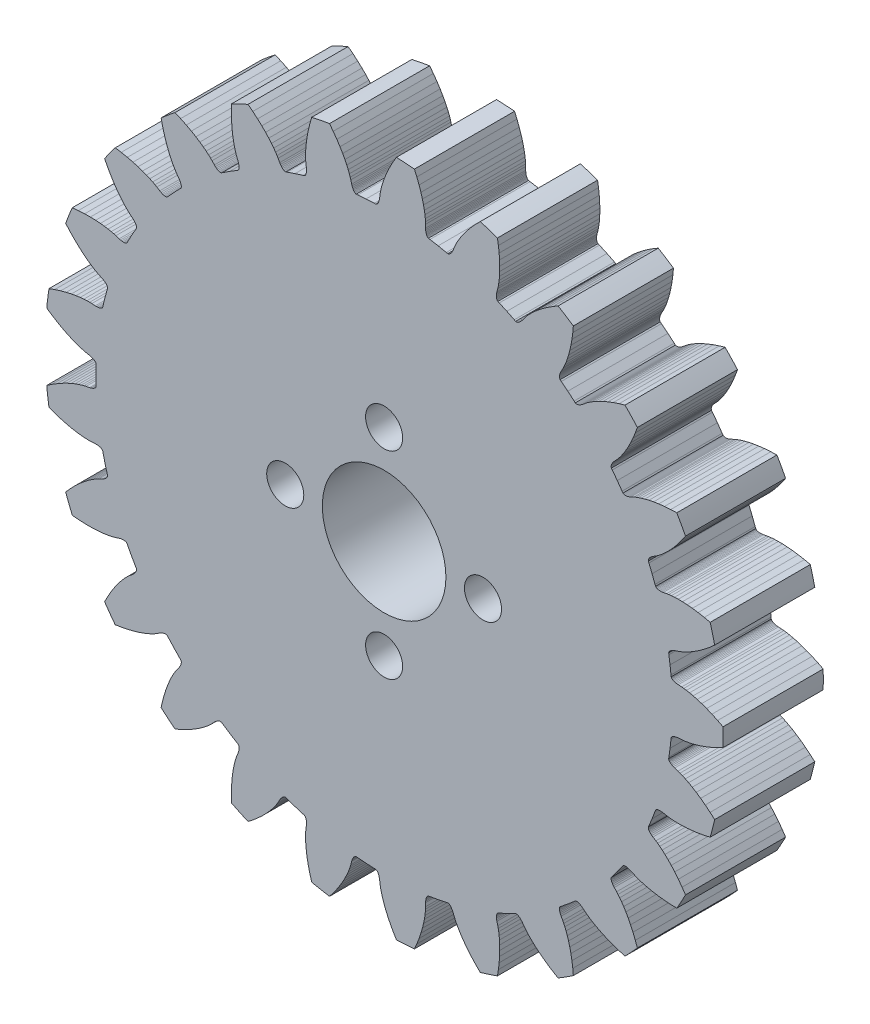
SolidWorks part; units mm, degrees
ref_plane "Front Plane" through (0, 0, 0) normal (0, 0, 1) x (1, 0, 0)
ref_plane "Top Plane" through (0, 0, 0) normal (0, 1, 0) x (1, 0, 0)
ref_plane "Right Plane" through (0, 0, 0) normal (1, 0, 0) x (0, 0, -1)
sketch "Sketch1" plane through (0, 0, 0) normal (0, 0, 1) x (1, 0, 0)
  line L0 (51.4459, 5.2739) -> (51.0519, 4.9541)
  line L1 (51.0519, 4.9541) -> (50.6785, 4.6761)
  line L2 (50.6785, 4.6761) -> (50.3269, 4.4365)
  line L3 (50.3269, 4.4365) -> (50.003, 4.2351)
  line L4 (50.003, 4.2351) -> (49.7071, 4.0679)
  line L5 (49.7071, 4.0679) -> (49.4414, 3.932)
  line L6 (49.4414, 3.932) -> (49.2085, 3.825)
  line L7 (49.2085, 3.825) -> (49.0099, 3.7435)
  line L8 (49.0099, 3.7435) -> (48.8471, 3.6846)
  line L9 (48.8471, 3.6846) -> (48.5824, 3.6)
  line L10 (48.5824, 3.6) -> (48.48, 3.5596)
  line L11 (48.48, 3.5596) -> (48.3896, 3.517)
  line L12 (48.3896, 3.517) -> (48.3112, 3.4725)
  line L13 (48.3112, 3.4725) -> (48.2449, 3.4268)
  line L14 (48.2449, 3.4268) -> (48.1907, 3.3803)
  line L15 (48.1907, 3.3803) -> (48.1486, 3.3335)
  line L16 (48.1486, 3.3335) -> (48.1186, 3.2869)
  line L17 (48.1186, 3.2869) -> (48.1007, 3.2409)
  line L18 (48.1007, 3.2409) -> (48.0947, 3.1961)
  line L19 (48.0947, 3.1961) -> (48.1121, 3.0744)
  line L20 (48.1121, 3.0744) -> (48.2057, 2.4097)
  line L21 (48.2057, 2.4097) -> (48.2803, 1.7426)
  line L22 (48.2803, 1.7426) -> (48.2938, 1.6204)
  line L23 (48.2938, 1.6204) -> (48.3107, 1.5784)
  line L24 (48.3107, 1.5784) -> (48.3395, 1.5384)
  line L25 (48.3395, 1.5384) -> (48.3802, 1.5007)
  line L26 (48.3802, 1.5007) -> (48.4326, 1.4658)
  line L27 (48.4326, 1.4658) -> (48.4966, 1.4342)
  line L28 (48.4966, 1.4342) -> (48.5722, 1.4064)
  line L29 (48.5722, 1.4064) -> (48.6592, 1.3829)
  line L30 (48.6592, 1.3829) -> (48.7573, 1.3641)
  line L31 (48.7573, 1.3641) -> (48.8666, 1.3504)
  line L32 (48.8666, 1.3504) -> (49.144, 1.3343)
  line L33 (49.144, 1.3343) -> (49.3163, 1.3177)
  line L34 (49.3163, 1.3177) -> (49.5289, 1.2882)
  line L35 (49.5289, 1.2882) -> (49.7812, 1.2424)
  line L36 (49.7812, 1.2424) -> (50.0723, 1.1769)
  line L37 (50.0723, 1.1769) -> (50.4005, 1.0885)
  line L38 (50.4005, 1.0885) -> (50.7643, 0.974)
  line L39 (50.7643, 0.974) -> (51.1644, 0.8294)
  line L40 (51.1644, 0.8294) -> (51.5953, 0.653)
  line L41 (51.5953, 0.653) -> (52.0565, 0.4412)
  line L42 (52.0565, 0.4412) -> (52.4946, 0.2183)
  line L43 (52.4946, -1.2438) -> (52.0565, -1.4667)
  line L44 (52.0565, -1.4667) -> (51.5953, -1.6785)
  line L45 (51.5953, -1.6785) -> (51.1644, -1.8549)
  line L46 (51.1644, -1.8549) -> (50.7643, -1.9995)
  line L47 (50.7643, -1.9995) -> (50.4005, -2.114)
  line L48 (50.4005, -2.114) -> (50.0723, -2.2024)
  line L49 (50.0723, -2.2024) -> (49.7812, -2.2679)
  line L50 (49.7812, -2.2679) -> (49.5289, -2.3137)
  line L51 (49.5289, -2.3137) -> (49.3163, -2.3432)
  line L52 (49.3163, -2.3432) -> (49.144, -2.3598)
  line L53 (49.144, -2.3598) -> (48.8666, -2.3759)
  line L54 (48.8666, -2.3759) -> (48.7573, -2.3896)
  line L55 (48.7573, -2.3896) -> (48.6592, -2.4084)
  line L56 (48.6592, -2.4084) -> (48.5722, -2.4319)
  line L57 (48.5722, -2.4319) -> (48.4966, -2.4597)
  line L58 (48.4966, -2.4597) -> (48.4326, -2.4913)
  line L59 (48.4326, -2.4913) -> (48.3802, -2.5262)
  line L60 (48.3802, -2.5262) -> (48.3395, -2.5639)
  line L61 (48.3395, -2.5639) -> (48.3107, -2.6039)
  line L62 (48.3107, -2.6039) -> (48.2938, -2.6459)
  line L63 (48.2938, -2.6459) -> (48.2803, -2.7681)
  line L64 (48.2803, -2.7681) -> (48.2057, -3.4352)
  line L65 (48.2057, -3.4352) -> (48.1121, -4.0999)
  line L66 (48.1121, -4.0999) -> (48.0947, -4.2216)
  line L67 (48.0947, -4.2216) -> (48.1007, -4.2664)
  line L68 (48.1007, -4.2664) -> (48.1186, -4.3124)
  line L69 (48.1186, -4.3124) -> (48.1486, -4.359)
  line L70 (48.1486, -4.359) -> (48.1907, -4.4058)
  line L71 (48.1907, -4.4058) -> (48.2449, -4.4523)
  line L72 (48.2449, -4.4523) -> (48.3112, -4.498)
  line L73 (48.3112, -4.498) -> (48.3896, -4.5425)
  line L74 (48.3896, -4.5425) -> (48.48, -4.5851)
  line L75 (48.48, -4.5851) -> (48.5824, -4.6255)
  line L76 (48.5824, -4.6255) -> (48.8471, -4.7101)
  line L77 (48.8471, -4.7101) -> (49.0099, -4.769)
  line L78 (49.0099, -4.769) -> (49.2085, -4.8505)
  line L79 (49.2085, -4.8505) -> (49.4414, -4.9575)
  line L80 (49.4414, -4.9575) -> (49.7071, -5.0934)
  line L81 (49.7071, -5.0934) -> (50.003, -5.2607)
  line L82 (50.003, -5.2607) -> (50.3269, -5.462)
  line L83 (50.3269, -5.462) -> (50.6785, -5.7016)
  line L84 (50.6785, -5.7016) -> (51.0519, -5.9796)
  line L85 (51.0519, -5.9796) -> (51.4459, -6.2994)
  line L86 (51.4459, -6.2994) -> (51.8149, -6.6243)
  line L87 (51.4513, -8.0404) -> (50.9715, -8.1474)
  line L88 (50.9715, -8.1474) -> (50.4721, -8.2379)
  line L89 (50.4721, -8.2379) -> (50.0109, -8.3016)
  line L90 (50.0109, -8.3016) -> (49.5874, -8.3422)
  line L91 (49.5874, -8.3422) -> (49.2066, -8.3626)
  line L92 (49.2066, -8.3626) -> (48.8667, -8.3666)
  line L93 (48.8667, -8.3666) -> (48.5684, -8.3576)
  line L94 (48.5684, -8.3576) -> (48.3127, -8.3392)
  line L95 (48.3127, -8.3392) -> (48.0995, -8.3149)
  line L96 (48.0995, -8.3149) -> (47.9284, -8.2882)
  line L97 (47.9284, -8.2882) -> (47.6557, -8.2348)
  line L98 (47.6557, -8.2348) -> (47.5465, -8.2208)
  line L99 (47.5465, -8.2208) -> (47.4467, -8.2146)
  line L100 (47.4467, -8.2146) -> (47.3566, -8.2158)
  line L101 (47.3566, -8.2158) -> (47.2765, -8.2239)
  line L102 (47.2765, -8.2239) -> (47.2066, -8.2386)
  line L103 (47.2066, -8.2386) -> (47.1472, -8.2593)
  line L104 (47.1472, -8.2593) -> (47.0984, -8.2857)
  line L105 (47.0984, -8.2857) -> (47.0606, -8.3174)
  line L106 (47.0606, -8.3174) -> (47.0338, -8.3538)
  line L107 (47.0338, -8.3538) -> (46.9903, -8.4688)
  line L108 (46.9903, -8.4688) -> (46.7521, -9.0964)
  line L109 (46.7521, -9.0964) -> (46.4961, -9.7169)
  line L110 (46.4961, -9.7169) -> (46.4491, -9.8305)
  line L111 (46.4491, -9.8305) -> (46.4437, -9.8754)
  line L112 (46.4437, -9.8754) -> (46.4497, -9.9244)
  line L113 (46.4497, -9.9244) -> (46.4671, -9.977)
  line L114 (46.4671, -9.977) -> (46.4963, -10.0328)
  line L115 (46.4963, -10.0328) -> (46.5372, -10.0913)
  line L116 (46.5372, -10.0913) -> (46.59, -10.1521)
  line L117 (46.59, -10.1521) -> (46.6549, -10.2146)
  line L118 (46.6549, -10.2146) -> (46.7318, -10.2784)
  line L119 (46.7318, -10.2784) -> (46.821, -10.343)
  line L120 (46.821, -10.343) -> (47.0563, -10.4908)
  line L121 (47.0563, -10.4908) -> (47.1993, -10.5884)
  line L122 (47.1993, -10.5884) -> (47.3715, -10.7166)
  line L123 (47.3715, -10.7166) -> (47.5704, -10.8782)
  line L124 (47.5704, -10.8782) -> (47.794, -11.0759)
  line L125 (47.794, -11.0759) -> (48.039, -11.3115)
  line L126 (48.039, -11.3115) -> (48.3027, -11.5871)
  line L127 (48.3027, -11.5871) -> (48.5836, -11.9065)
  line L128 (48.5836, -11.9065) -> (48.8762, -12.2687)
  line L129 (48.8762, -12.2687) -> (49.1783, -12.6765)
  line L130 (49.1783, -12.6765) -> (49.4548, -13.0829)
  line L131 (48.7505, -14.3641) -> (48.2591, -14.3484)
  line L132 (48.2591, -14.3484) -> (47.7529, -14.3118)
  line L133 (47.7529, -14.3118) -> (47.2904, -14.2589)
  line L134 (47.2904, -14.2589) -> (46.8702, -14.1928)
  line L135 (46.8702, -14.1928) -> (46.4962, -14.1179)
  line L136 (46.4962, -14.1179) -> (46.166, -14.0372)
  line L137 (46.166, -14.0372) -> (45.8793, -13.9544)
  line L138 (45.8793, -13.9544) -> (45.6362, -13.873)
  line L139 (45.6362, -13.873) -> (45.4357, -13.7964)
  line L140 (45.4357, -13.7964) -> (45.2767, -13.728)
  line L141 (45.2767, -13.728) -> (45.0258, -13.6084)
  line L142 (45.0258, -13.6084) -> (44.9235, -13.5677)
  line L143 (44.9235, -13.5677) -> (44.8284, -13.5369)
  line L144 (44.8284, -13.5369) -> (44.7408, -13.5157)
  line L145 (44.7408, -13.5157) -> (44.6612, -13.5036)
  line L146 (44.6612, -13.5036) -> (44.5899, -13.5004)
  line L147 (44.5899, -13.5004) -> (44.5272, -13.5057)
  line L148 (44.5272, -13.5057) -> (44.4734, -13.5192)
  line L149 (44.4734, -13.5192) -> (44.4288, -13.5404)
  line L150 (44.4288, -13.5404) -> (44.3938, -13.569)
  line L151 (44.3938, -13.569) -> (44.3231, -13.6696)
  line L152 (44.3231, -13.6696) -> (43.9364, -14.2183)
  line L153 (43.9364, -14.2183) -> (43.5341, -14.7556)
  line L154 (43.5341, -14.7556) -> (43.4603, -14.8539)
  line L155 (43.4603, -14.8539) -> (43.4439, -14.8961)
  line L156 (43.4439, -14.8961) -> (43.4375, -14.945)
  line L157 (43.4375, -14.945) -> (43.4413, -15.0003)
  line L158 (43.4413, -15.0003) -> (43.4556, -15.0616)
  line L159 (43.4556, -15.0616) -> (43.4807, -15.1285)
  line L160 (43.4807, -15.1285) -> (43.5168, -15.2005)
  line L161 (43.5168, -15.2005) -> (43.564, -15.2772)
  line L162 (43.564, -15.2772) -> (43.6227, -15.3581)
  line L163 (43.6227, -15.3581) -> (43.693, -15.4429)
  line L164 (43.693, -15.4429) -> (43.8842, -15.6445)
  line L165 (43.8842, -15.6445) -> (43.9985, -15.7746)
  line L166 (43.9985, -15.7746) -> (44.1333, -15.9416)
  line L167 (44.1333, -15.9416) -> (44.2858, -16.1476)
  line L168 (44.2858, -16.1476) -> (44.4532, -16.3947)
  line L169 (44.4532, -16.3947) -> (44.6319, -16.6838)
  line L170 (44.6319, -16.6838) -> (44.8188, -17.0163)
  line L171 (44.8188, -17.0163) -> (45.0115, -17.3956)
  line L172 (45.0115, -17.3956) -> (45.2047, -17.8191)
  line L173 (45.2047, -17.8191) -> (45.3959, -18.2892)
  line L174 (45.3959, -18.2892) -> (45.5627, -18.7517)
  line L175 (44.5619, -19.8175) -> (44.0899, -19.6801)
  line L176 (44.0899, -19.6801) -> (43.6087, -19.5187)
  line L177 (43.6087, -19.5187) -> (43.1739, -19.3524)
  line L178 (43.1739, -19.3524) -> (42.7832, -19.1839)
  line L179 (42.7832, -19.1839) -> (42.4397, -19.0184)
  line L180 (42.4397, -19.0184) -> (42.1399, -18.8581)
  line L181 (42.1399, -18.8581) -> (41.8828, -18.7066)
  line L182 (41.8828, -18.7066) -> (41.6676, -18.5673)
  line L183 (41.6676, -18.5673) -> (41.4924, -18.4432)
  line L184 (41.4924, -18.4432) -> (41.3554, -18.3374)
  line L185 (41.3554, -18.3374) -> (41.1422, -18.1592)
  line L186 (41.1422, -18.1592) -> (41.0532, -18.0944)
  line L187 (41.0532, -18.0944) -> (40.9687, -18.0409)
  line L188 (40.9687, -18.0409) -> (40.8892, -17.9985)
  line L189 (40.8892, -17.9985) -> (40.8151, -17.9671)
  line L190 (40.8151, -17.9671) -> (40.7468, -17.9462)
  line L191 (40.7468, -17.9462) -> (40.6848, -17.9358)
  line L192 (40.6848, -17.9358) -> (40.6293, -17.9354)
  line L193 (40.6293, -17.9354) -> (40.5809, -17.9449)
  line L194 (40.5809, -17.9449) -> (40.5398, -17.9639)
  line L195 (40.5398, -17.9639) -> (40.4463, -18.0437)
  line L196 (40.4463, -18.0437) -> (39.9353, -18.479)
  line L197 (39.9353, -18.479) -> (39.412, -18.8994)
  line L198 (39.412, -18.8994) -> (39.3161, -18.9763)
  line L199 (39.3161, -18.9763) -> (39.2897, -19.013)
  line L200 (39.2897, -19.013) -> (39.2713, -19.0588)
  line L201 (39.2713, -19.0588) -> (39.2613, -19.1134)
  line L202 (39.2613, -19.1134) -> (39.2599, -19.1763)
  line L203 (39.2599, -19.1763) -> (39.2676, -19.2473)
  line L204 (39.2676, -19.2473) -> (39.2846, -19.326)
  line L205 (39.2846, -19.326) -> (39.3113, -19.412)
  line L206 (39.3113, -19.412) -> (39.348, -19.505)
  line L207 (39.348, -19.505) -> (39.3951, -19.6046)
  line L208 (39.3951, -19.6046) -> (39.5301, -19.8474)
  line L209 (39.5301, -19.8474) -> (39.6084, -20.0018)
  line L210 (39.6084, -20.0018) -> (39.6975, -20.1971)
  line L211 (39.6975, -20.1971) -> (39.7939, -20.4346)
  line L212 (39.7939, -20.4346) -> (39.8946, -20.7155)
  line L213 (39.8946, -20.7155) -> (39.9959, -21.04)
  line L214 (39.9959, -21.04) -> (40.0941, -21.4086)
  line L215 (40.0941, -21.4086) -> (40.1864, -21.8238)
  line L216 (40.1864, -21.8238) -> (40.2683, -22.2821)
  line L217 (40.2683, -22.2821) -> (40.3366, -22.785)
  line L218 (40.3366, -22.785) -> (40.3831, -23.2744)
  line L219 (39.1487, -24.0578) -> (38.7257, -23.8073)
  line L220 (38.7257, -23.8073) -> (38.2998, -23.5314)
  line L221 (38.2998, -23.5314) -> (37.9199, -23.2622)
  line L222 (37.9199, -23.2622) -> (37.5835, -23.0019)
  line L223 (37.5835, -23.0019) -> (37.2919, -22.756)
  line L224 (37.2919, -22.756) -> (37.0414, -22.5263)
  line L225 (37.0414, -22.5263) -> (36.83, -22.3156)
  line L226 (36.83, -22.3156) -> (36.6562, -22.1271)
  line L227 (36.6562, -22.1271) -> (36.5174, -21.9634)
  line L228 (36.5174, -21.9634) -> (36.4111, -21.8268)
  line L229 (36.4111, -21.8268) -> (36.2488, -21.6012)
  line L230 (36.2488, -21.6012) -> (36.1788, -21.5163)
  line L231 (36.1788, -21.5163) -> (36.1102, -21.4435)
  line L232 (36.1102, -21.4435) -> (36.0438, -21.3827)
  line L233 (36.0438, -21.3827) -> (35.9798, -21.3338)
  line L234 (35.9798, -21.3338) -> (35.9189, -21.2966)
  line L235 (35.9189, -21.2966) -> (35.8613, -21.271)
  line L236 (35.8613, -21.271) -> (35.8077, -21.2569)
  line L237 (35.8077, -21.2569) -> (35.7584, -21.254)
  line L238 (35.7584, -21.254) -> (35.714, -21.2622)
  line L239 (35.714, -21.2622) -> (35.6036, -21.3163)
  line L240 (35.6036, -21.3163) -> (35.0003, -21.6108)
  line L241 (35.0003, -21.6108) -> (34.3889, -21.8879)
  line L242 (34.3889, -21.8879) -> (34.2769, -21.9385)
  line L243 (34.2769, -21.9385) -> (34.2422, -21.9675)
  line L244 (34.2422, -21.9675) -> (34.213, -22.0073)
  line L245 (34.213, -22.0073) -> (34.1897, -22.0576)
  line L246 (34.1897, -22.0576) -> (34.1728, -22.1183)
  line L247 (34.1728, -22.1183) -> (34.1625, -22.1889)
  line L248 (34.1625, -22.1889) -> (34.1595, -22.2694)
  line L249 (34.1595, -22.2694) -> (34.1639, -22.3593)
  line L250 (34.1639, -22.3593) -> (34.1764, -22.4585)
  line L251 (34.1764, -22.4585) -> (34.1971, -22.5667)
  line L252 (34.1971, -22.5667) -> (34.2676, -22.8355)
  line L253 (34.2676, -22.8355) -> (34.305, -23.0045)
  line L254 (34.305, -23.0045) -> (34.3427, -23.2158)
  line L255 (34.3427, -23.2158) -> (34.3771, -23.4698)
  line L256 (34.3771, -23.4698) -> (34.4047, -23.767)
  line L257 (34.4047, -23.767) -> (34.4221, -24.1065)
  line L258 (34.4221, -24.1065) -> (34.4256, -24.4878)
  line L259 (34.4256, -24.4878) -> (34.4117, -24.913)
  line L260 (34.4117, -24.913) -> (34.3771, -25.3773)
  line L261 (34.3771, -25.3773) -> (34.3182, -25.8814)
  line L262 (34.3182, -25.8814) -> (34.2415, -26.3669)
  line L263 (32.851, -26.8187) -> (32.5036, -26.471)
  line L264 (32.5036, -26.471) -> (32.1597, -26.0978)
  line L265 (32.1597, -26.0978) -> (31.8588, -25.7426)
  line L266 (31.8588, -25.7426) -> (31.5976, -25.4067)
  line L267 (31.5976, -25.4067) -> (31.3763, -25.0961)
  line L268 (31.3763, -25.0961) -> (31.1908, -24.8113)
  line L269 (31.1908, -24.8113) -> (31.0385, -24.5546)
  line L270 (31.0385, -24.5546) -> (30.917, -24.3289)
  line L271 (30.917, -24.3289) -> (30.8233, -24.1358)
  line L272 (30.8233, -24.1358) -> (30.7542, -23.977)
  line L273 (30.7542, -23.977) -> (30.6532, -23.7182)
  line L274 (30.6532, -23.7182) -> (30.6065, -23.6185)
  line L275 (30.6065, -23.6185) -> (30.5582, -23.5309)
  line L276 (30.5582, -23.5309) -> (30.5089, -23.4555)
  line L277 (30.5089, -23.4555) -> (30.4592, -23.3922)
  line L278 (30.4592, -23.3922) -> (30.4094, -23.3411)
  line L279 (30.4094, -23.3411) -> (30.36, -23.302)
  line L280 (30.36, -23.302) -> (30.3116, -23.275)
  line L281 (30.3116, -23.275) -> (30.2646, -23.2599)
  line L282 (30.2646, -23.2599) -> (30.2195, -23.2568)
  line L283 (30.2195, -23.2568) -> (30.0991, -23.2818)
  line L284 (30.0991, -23.2818) -> (29.4416, -23.4169)
  line L285 (29.4416, -23.4169) -> (28.7805, -23.5333)
  line L286 (28.7805, -23.5333) -> (28.6593, -23.5544)
  line L287 (28.6593, -23.5544) -> (28.6185, -23.5739)
  line L288 (28.6185, -23.5739) -> (28.5804, -23.6052)
  line L289 (28.5804, -23.6052) -> (28.5453, -23.6482)
  line L290 (28.5453, -23.6482) -> (28.5138, -23.7027)
  line L291 (28.5138, -23.7027) -> (28.4863, -23.7686)
  line L292 (28.4863, -23.7686) -> (28.4633, -23.8457)
  line L293 (28.4633, -23.8457) -> (28.4453, -23.934)
  line L294 (28.4453, -23.934) -> (28.4326, -24.0332)
  line L295 (28.4326, -24.0332) -> (28.4259, -24.1431)
  line L296 (28.4259, -24.1431) -> (28.4272, -24.4209)
  line L297 (28.4272, -24.4209) -> (28.4215, -24.594)
  line L298 (28.4215, -24.594) -> (28.4054, -24.808)
  line L299 (28.4054, -24.808) -> (28.3756, -25.0626)
  line L300 (28.3756, -25.0626) -> (28.3285, -25.3573)
  line L301 (28.3285, -25.3573) -> (28.2608, -25.6904)
  line L302 (28.2608, -25.6904) -> (28.1694, -26.0607)
  line L303 (28.1694, -26.0607) -> (28.0502, -26.4691)
  line L304 (28.0502, -26.4691) -> (27.9012, -26.9101)
  line L305 (27.9012, -26.9101) -> (27.7188, -27.3837)
  line L306 (27.7188, -27.3837) -> (27.5238, -27.835)
  line L307 (26.0646, -27.9268) -> (25.8146, -27.5035)
  line L308 (25.8146, -27.5035) -> (25.5743, -27.0565)
  line L309 (25.5743, -27.0565) -> (25.3711, -26.6376)
  line L310 (25.3711, -26.6376) -> (25.2017, -26.2474)
  line L311 (25.2017, -26.2474) -> (25.0646, -25.8915)
  line L312 (25.0646, -25.8915) -> (24.9558, -25.5695)
  line L313 (24.9558, -25.5695) -> (24.8721, -25.283)
  line L314 (24.8721, -25.283) -> (24.8106, -25.0342)
  line L315 (24.8106, -25.0342) -> (24.7678, -24.8238)
  line L316 (24.7678, -24.8238) -> (24.7404, -24.6529)
  line L317 (24.7404, -24.6529) -> (24.7069, -24.377)
  line L318 (24.7069, -24.377) -> (24.6864, -24.2688)
  line L319 (24.6864, -24.2688) -> (24.6615, -24.172)
  line L320 (24.6615, -24.172) -> (24.6325, -24.0867)
  line L321 (24.6325, -24.0867) -> (24.6, -24.0131)
  line L322 (24.6, -24.0131) -> (24.5645, -23.9511)
  line L323 (24.5645, -23.9511) -> (24.5264, -23.901)
  line L324 (24.5264, -23.901) -> (24.4862, -23.8628)
  line L325 (24.4862, -23.8628) -> (24.4445, -23.8366)
  line L326 (24.4445, -23.8366) -> (24.4015, -23.8223)
  line L327 (24.4015, -23.8223) -> (24.2787, -23.8165)
  line L328 (24.2787, -23.8165) -> (23.6083, -23.7839)
  line L329 (23.6083, -23.7839) -> (22.939, -23.7322)
  line L330 (22.939, -23.7322) -> (22.8164, -23.7226)
  line L331 (22.8164, -23.7226) -> (22.7721, -23.7313)
  line L332 (22.7721, -23.7313) -> (22.7273, -23.7521)
  line L333 (22.7273, -23.7521) -> (22.6826, -23.785)
  line L334 (22.6826, -23.785) -> (22.6386, -23.83)
  line L335 (22.6386, -23.83) -> (22.5956, -23.8869)
  line L336 (22.5956, -23.8869) -> (22.5541, -23.956)
  line L337 (22.5541, -23.956) -> (22.5147, -24.037)
  line L338 (22.5147, -24.037) -> (22.4778, -24.1299)
  line L339 (22.4778, -24.1299) -> (22.4439, -24.2347)
  line L340 (22.4439, -24.2347) -> (22.3761, -24.5041)
  line L341 (22.3761, -24.5041) -> (22.3275, -24.6703)
  line L342 (22.3275, -24.6703) -> (22.2587, -24.8736)
  line L343 (22.2587, -24.8736) -> (22.1665, -25.1128)
  line L344 (22.1665, -25.1128) -> (22.0476, -25.3865)
  line L345 (22.0476, -25.3865) -> (21.8992, -25.6923)
  line L346 (21.8992, -25.6923) -> (21.7186, -26.0283)
  line L347 (21.7186, -26.0283) -> (21.5016, -26.3942)
  line L348 (21.5016, -26.3942) -> (21.2476, -26.7843)
  line L349 (21.2476, -26.7843) -> (20.9531, -27.1976)
  line L350 (20.9531, -27.1976) -> (20.652, -27.5862)
  line L351 (19.2159, -27.3123) -> (19.079, -26.8401)
  line L352 (19.079, -26.8401) -> (18.9573, -26.3474)
  line L353 (18.9573, -26.3474) -> (18.8648, -25.8912)
  line L354 (18.8648, -25.8912) -> (18.7977, -25.4711)
  line L355 (18.7977, -25.4711) -> (18.7534, -25.0922)
  line L356 (18.7534, -25.0922) -> (18.7281, -24.7533)
  line L357 (18.7281, -24.7533) -> (18.7183, -24.455)
  line L358 (18.7183, -24.455) -> (18.7206, -24.1987)
  line L359 (18.7206, -24.1987) -> (18.7315, -23.9843)
  line L360 (18.7315, -23.9843) -> (18.7474, -23.8119)
  line L361 (18.7474, -23.8119) -> (18.7836, -23.5364)
  line L362 (18.7836, -23.5364) -> (18.7907, -23.4265)
  line L363 (18.7907, -23.4265) -> (18.7906, -23.3266)
  line L364 (18.7906, -23.3266) -> (18.7837, -23.2367)
  line L365 (18.7837, -23.2367) -> (18.7706, -23.1573)
  line L366 (18.7706, -23.1573) -> (18.7516, -23.0885)
  line L367 (18.7516, -23.0885) -> (18.7272, -23.0305)
  line L368 (18.7272, -23.0305) -> (18.6977, -22.9835)
  line L369 (18.6977, -22.9835) -> (18.6638, -22.9476)
  line L370 (18.6638, -22.9476) -> (18.6258, -22.9232)
  line L371 (18.6258, -22.9232) -> (18.5082, -22.887)
  line L372 (18.5082, -22.887) -> (17.8669, -22.6887)
  line L373 (17.8669, -22.6887) -> (17.2316, -22.4722)
  line L374 (17.2316, -22.4722) -> (17.1152, -22.4324)
  line L375 (17.1152, -22.4324) -> (17.0701, -22.4298)
  line L376 (17.0701, -22.4298) -> (17.0216, -22.4388)
  line L377 (17.0216, -22.4388) -> (16.9701, -22.4596)
  line L378 (16.9701, -22.4596) -> (16.9163, -22.4921)
  line L379 (16.9163, -22.4921) -> (16.8604, -22.5367)
  line L380 (16.8604, -22.5367) -> (16.8031, -22.5932)
  line L381 (16.8031, -22.5932) -> (16.7448, -22.6619)
  line L382 (16.7448, -22.6619) -> (16.686, -22.7427)
  line L383 (16.686, -22.7427) -> (16.6271, -22.8357)
  line L384 (16.6271, -22.8357) -> (16.4944, -23.0799)
  line L385 (16.4944, -23.0799) -> (16.406, -23.2287)
  line L386 (16.406, -23.2287) -> (16.2888, -23.4086)
  line L387 (16.2888, -23.4086) -> (16.14, -23.6173)
  line L388 (16.14, -23.6173) -> (15.9568, -23.8528)
  line L389 (15.9568, -23.8528) -> (15.737, -24.1122)
  line L390 (15.737, -24.1122) -> (15.4785, -24.3926)
  line L391 (15.4785, -24.3926) -> (15.1773, -24.6931)
  line L392 (15.1773, -24.6931) -> (14.8343, -25.0078)
  line L393 (14.8343, -25.0078) -> (14.4462, -25.3349)
  line L394 (14.4462, -25.3349) -> (14.058, -25.6364)
  line L395 (12.7351, -25.0139) -> (12.7199, -24.5225)
  line L396 (12.7199, -24.5225) -> (12.7246, -24.015)
  line L397 (12.7246, -24.015) -> (12.7484, -23.5501)
  line L398 (12.7484, -23.5501) -> (12.788, -23.1265)
  line L399 (12.788, -23.1265) -> (12.8393, -22.7486)
  line L400 (12.8393, -22.7486) -> (12.899, -22.414)
  line L401 (12.899, -22.414) -> (12.9637, -22.1226)
  line L402 (12.9637, -22.1226) -> (13.0297, -21.8749)
  line L403 (13.0297, -21.8749) -> (13.0935, -21.67)
  line L404 (13.0935, -21.67) -> (13.1519, -21.507)
  line L405 (13.1519, -21.507) -> (13.2554, -21.2491)
  line L406 (13.2554, -21.2491) -> (13.2896, -21.1445)
  line L407 (13.2896, -21.1445) -> (13.3144, -21.0476)
  line L408 (13.3144, -21.0476) -> (13.3301, -20.9589)
  line L409 (13.3301, -20.9589) -> (13.3371, -20.8787)
  line L410 (13.3371, -20.8787) -> (13.3358, -20.8073)
  line L411 (13.3358, -20.8073) -> (13.3266, -20.745)
  line L412 (13.3266, -20.745) -> (13.3098, -20.6922)
  line L413 (13.3098, -20.6922) -> (13.2858, -20.6491)
  line L414 (13.2858, -20.6491) -> (13.255, -20.6159)
  line L415 (13.255, -20.6159) -> (13.1502, -20.5517)
  line L416 (13.1502, -20.5517) -> (12.5784, -20.2001)
  line L417 (12.5784, -20.2001) -> (12.0168, -19.8324)
  line L418 (12.0168, -19.8324) -> (11.914, -19.7649)
  line L419 (11.914, -19.7649) -> (11.8709, -19.7512)
  line L420 (11.8709, -19.7512) -> (11.8217, -19.7478)
  line L421 (11.8217, -19.7478) -> (11.7667, -19.7551)
  line L422 (11.7667, -19.7551) -> (11.7065, -19.7733)
  line L423 (11.7065, -19.7733) -> (11.6413, -19.8025)
  line L424 (11.6413, -19.8025) -> (11.5717, -19.843)
  line L425 (11.5717, -19.843) -> (11.4982, -19.895)
  line L426 (11.4982, -19.895) -> (11.4211, -19.9587)
  line L427 (11.4211, -19.9587) -> (11.3409, -20.0341)
  line L428 (11.3409, -20.0341) -> (11.1517, -20.2376)
  line L429 (11.1517, -20.2376) -> (11.029, -20.3598)
  line L430 (11.029, -20.3598) -> (10.8708, -20.5049)
  line L431 (10.8708, -20.5049) -> (10.6748, -20.67)
  line L432 (10.6748, -20.67) -> (10.4387, -20.8526)
  line L433 (10.4387, -20.8526) -> (10.1614, -21.0491)
  line L434 (10.1614, -21.0491) -> (9.8412, -21.2565)
  line L435 (9.8412, -21.2565) -> (9.4748, -21.4726)
  line L436 (9.4748, -21.4726) -> (9.0642, -21.6921)
  line L437 (9.0642, -21.6921) -> (8.6071, -21.9124)
  line L438 (8.6071, -21.9124) -> (8.156, -22.1079)
  line L439 (7.0295, -21.176) -> (7.137, -20.6963)
  line L440 (7.137, -20.6963) -> (7.2678, -20.2059)
  line L441 (7.2678, -20.2059) -> (7.4065, -19.7615)
  line L442 (7.4065, -19.7615) -> (7.5501, -19.3611)
  line L443 (7.5501, -19.3611) -> (7.6938, -19.0078)
  line L444 (7.6938, -19.0078) -> (7.8349, -18.6985)
  line L445 (7.8349, -18.6985) -> (7.97, -18.4324)
  line L446 (7.97, -18.4324) -> (8.0955, -18.2089)
  line L447 (8.0955, -18.2089) -> (8.2083, -18.0263)
  line L448 (8.2083, -18.0263) -> (8.3053, -17.8829)
  line L449 (8.3053, -17.8829) -> (8.4697, -17.6589)
  line L450 (8.4697, -17.6589) -> (8.5289, -17.566)
  line L451 (8.5289, -17.566) -> (8.5769, -17.4784)
  line L452 (8.5769, -17.4784) -> (8.6142, -17.3964)
  line L453 (8.6142, -17.3964) -> (8.641, -17.3204)
  line L454 (8.641, -17.3204) -> (8.6575, -17.251)
  line L455 (8.6575, -17.251) -> (8.664, -17.1883)
  line L456 (8.664, -17.1883) -> (8.6609, -17.133)
  line L457 (8.6609, -17.133) -> (8.6484, -17.0852)
  line L458 (8.6484, -17.0852) -> (8.6269, -17.0455)
  line L459 (8.6269, -17.0455) -> (8.5413, -16.9572)
  line L460 (8.5413, -16.9572) -> (8.0748, -16.4745)
  line L461 (8.0748, -16.4745) -> (7.6224, -15.9786)
  line L462 (7.6224, -15.9786) -> (7.5396, -15.8877)
  line L463 (7.5396, -15.8877) -> (7.5013, -15.8637)
  line L464 (7.5013, -15.8637) -> (7.4544, -15.8482)
  line L465 (7.4544, -15.8482) -> (7.3994, -15.8416)
  line L466 (7.3994, -15.8416) -> (7.3365, -15.8442)
  line L467 (7.3365, -15.8442) -> (7.2661, -15.8563)
  line L468 (7.2661, -15.8563) -> (7.1887, -15.8783)
  line L469 (7.1887, -15.8783) -> (7.1045, -15.9103)
  line L470 (7.1045, -15.9103) -> (7.014, -15.9528)
  line L471 (7.014, -15.9528) -> (6.9175, -16.006)
  line L472 (6.9175, -16.006) -> (6.6836, -16.156)
  line L473 (6.6836, -16.156) -> (6.5345, -16.2439)
  line L474 (6.5345, -16.2439) -> (6.3451, -16.345)
  line L475 (6.3451, -16.345) -> (6.1142, -16.4562)
  line L476 (6.1142, -16.4562) -> (5.8401, -16.5743)
  line L477 (5.8401, -16.5743) -> (5.5226, -16.6957)
  line L478 (5.5226, -16.6957) -> (5.161, -16.817)
  line L479 (5.161, -16.817) -> (4.7523, -16.9351)
  line L480 (4.7523, -16.9351) -> (4.3001, -17.0456)
  line L481 (4.3001, -17.0456) -> (3.8025, -17.1454)
  line L482 (3.8025, -17.1454) -> (3.317, -17.2226)
  line L483 (2.4576, -16.0397) -> (2.681, -15.6018)
  line L484 (2.681, -15.6018) -> (2.9296, -15.1594)
  line L485 (2.9296, -15.1594) -> (3.1745, -14.7634)
  line L486 (3.1745, -14.7634) -> (3.4132, -14.4113)
  line L487 (3.4132, -14.4113) -> (3.6402, -14.1048)
  line L488 (3.6402, -14.1048) -> (3.8538, -13.8404)
  line L489 (3.8538, -13.8404) -> (4.0508, -13.6162)
  line L490 (4.0508, -13.6162) -> (4.228, -13.431)
  line L491 (4.228, -13.431) -> (4.3826, -13.2822)
  line L492 (4.3826, -13.2822) -> (4.5123, -13.1674)
  line L493 (4.5123, -13.1674) -> (4.7273, -12.9913)
  line L494 (4.7273, -12.9913) -> (4.8076, -12.9161)
  line L495 (4.8076, -12.9161) -> (4.876, -12.8431)
  line L496 (4.876, -12.8431) -> (4.9325, -12.773)
  line L497 (4.9325, -12.773) -> (4.9773, -12.7061)
  line L498 (4.9773, -12.7061) -> (5.0106, -12.6429)
  line L499 (5.0106, -12.6429) -> (5.0325, -12.5839)
  line L500 (5.0325, -12.5839) -> (5.0432, -12.5295)
  line L501 (5.0432, -12.5295) -> (5.043, -12.4801)
  line L502 (5.043, -12.4801) -> (5.032, -12.4362)
  line L503 (5.032, -12.4362) -> (4.9711, -12.3295)
  line L504 (4.9711, -12.3295) -> (4.6393, -11.7459)
  line L505 (4.6393, -11.7459) -> (4.3244, -11.1531)
  line L506 (4.3244, -11.1531) -> (4.2669, -11.0445)
  line L507 (4.2669, -11.0445) -> (4.2357, -11.0117)
  line L508 (4.2357, -11.0117) -> (4.1942, -10.985)
  line L509 (4.1942, -10.985) -> (4.1425, -10.965)
  line L510 (4.1425, -10.965) -> (4.0809, -10.9518)
  line L511 (4.0809, -10.9518) -> (4.0097, -10.9461)
  line L512 (4.0097, -10.9461) -> (3.9293, -10.948)
  line L513 (3.9293, -10.948) -> (3.8397, -10.9582)
  line L514 (3.8397, -10.9582) -> (3.7415, -10.9768)
  line L515 (3.7415, -10.9768) -> (3.6349, -11.0043)
  line L516 (3.6349, -11.0043) -> (3.371, -11.0915)
  line L517 (3.371, -11.0915) -> (3.2047, -11.1395)
  line L518 (3.2047, -11.1395) -> (2.9962, -11.1903)
  line L519 (2.9962, -11.1903) -> (2.7448, -11.2406)
  line L520 (2.7448, -11.2406) -> (2.45, -11.2869)
  line L521 (2.45, -11.2869) -> (2.1123, -11.3255)
  line L522 (2.1123, -11.3255) -> (1.7319, -11.353)
  line L523 (1.7319, -11.353) -> (1.3066, -11.3658)
  line L524 (1.3066, -11.3658) -> (0.8411, -11.3604)
  line L525 (0.8411, -11.3604) -> (0.3343, -11.3332)
  line L526 (0.3343, -11.3332) -> (-0.1551, -11.2872)
  line L527 (-0.6933, -9.9279) -> (-0.368, -9.5593)
  line L528 (-0.368, -9.5593) -> (-0.0172, -9.1926)
  line L529 (-0.0172, -9.1926) -> (0.3185, -8.87)
  line L530 (0.3185, -8.87) -> (0.6372, -8.5882)
  line L531 (0.6372, -8.5882) -> (0.9333, -8.3479)
  line L532 (0.9333, -8.3479) -> (1.206, -8.1448)
  line L533 (1.206, -8.1448) -> (1.4526, -7.9767)
  line L534 (1.4526, -7.9767) -> (1.6702, -7.8413)
  line L535 (1.6702, -7.8413) -> (1.857, -7.7357)
  line L536 (1.857, -7.7357) -> (2.0111, -7.6568)
  line L537 (2.0111, -7.6568) -> (2.2632, -7.5397)
  line L538 (2.2632, -7.5397) -> (2.3597, -7.4868)
  line L539 (2.3597, -7.4868) -> (2.4441, -7.4331)
  line L540 (2.4441, -7.4331) -> (2.5163, -7.3792)
  line L541 (2.5163, -7.3792) -> (2.5763, -7.3256)
  line L542 (2.5763, -7.3256) -> (2.6242, -7.2726)
  line L543 (2.6242, -7.2726) -> (2.6601, -7.2209)
  line L544 (2.6601, -7.2209) -> (2.684, -7.1709)
  line L545 (2.684, -7.1709) -> (2.6961, -7.123)
  line L546 (2.6961, -7.123) -> (2.6964, -7.0778)
  line L547 (2.6964, -7.0778) -> (2.6639, -6.9592)
  line L548 (2.6639, -6.9592) -> (2.4877, -6.3115)
  line L549 (2.4877, -6.3115) -> (2.3301, -5.659)
  line L550 (2.3301, -5.659) -> (2.3014, -5.5395)
  line L551 (2.3014, -5.5395) -> (2.2793, -5.5)
  line L552 (2.2793, -5.5) -> (2.2457, -5.4638)
  line L553 (2.2457, -5.4638) -> (2.2007, -5.4315)
  line L554 (2.2007, -5.4315) -> (2.1443, -5.4035)
  line L555 (2.1443, -5.4035) -> (2.0768, -5.3802)
  line L556 (2.0768, -5.3802) -> (1.9984, -5.3621)
  line L557 (1.9984, -5.3621) -> (1.9091, -5.3497)
  line L558 (1.9091, -5.3497) -> (1.8094, -5.3433)
  line L559 (1.8094, -5.3433) -> (1.6992, -5.3434)
  line L560 (1.6992, -5.3434) -> (1.422, -5.3622)
  line L561 (1.422, -5.3622) -> (1.2489, -5.3673)
  line L562 (1.2489, -5.3673) -> (1.0343, -5.3647)
  line L563 (1.0343, -5.3647) -> (0.7784, -5.3509)
  line L564 (0.7784, -5.3509) -> (0.4813, -5.3224)
  line L565 (0.4813, -5.3224) -> (0.1446, -5.2759)
  line L566 (0.1446, -5.2759) -> (-0.2307, -5.2079)
  line L567 (-0.2307, -5.2079) -> (-0.6458, -5.1146)
  line L568 (-0.6458, -5.1146) -> (-1.0953, -4.9935)
  line L569 (-1.0953, -4.9935) -> (-1.5794, -4.8412)
  line L570 (-1.5794, -4.8412) -> (-2.042, -4.6749)
  line L571 (-2.2253, -3.2244) -> (-1.8185, -2.9483)
  line L572 (-1.8185, -2.9483) -> (-1.3875, -2.6804)
  line L573 (-1.3875, -2.6804) -> (-0.9822, -2.4514)
  line L574 (-0.9822, -2.4514) -> (-0.6034, -2.2578)
  line L575 (-0.6034, -2.2578) -> (-0.2568, -2.0986)
  line L576 (-0.2568, -2.0986) -> (0.0578, -1.9697)
  line L577 (0.0578, -1.9697) -> (0.3384, -1.8682)
  line L578 (0.3384, -1.8682) -> (0.5829, -1.7912)
  line L579 (0.5829, -1.7912) -> (0.7901, -1.7353)
  line L580 (0.7901, -1.7353) -> (0.959, -1.6972)
  line L581 (0.959, -1.6972) -> (1.2322, -1.6465)
  line L582 (1.2322, -1.6465) -> (1.3389, -1.6193)
  line L583 (1.3389, -1.6193) -> (1.434, -1.5883)
  line L584 (1.434, -1.5883) -> (1.5173, -1.554)
  line L585 (1.5173, -1.554) -> (1.5888, -1.517)
  line L586 (1.5888, -1.517) -> (1.6483, -1.4776)
  line L587 (1.6483, -1.4776) -> (1.696, -1.4365)
  line L588 (1.696, -1.4365) -> (1.7316, -1.394)
  line L589 (1.7316, -1.394) -> (1.7552, -1.3506)
  line L590 (1.7552, -1.3506) -> (1.7667, -1.3069)
  line L591 (1.7667, -1.3069) -> (1.7647, -1.1839)
  line L592 (1.7647, -1.1839) -> (1.7552, -0.5128)
  line L593 (1.7552, -0.5128) -> (1.7647, 0.1584)
  line L594 (1.7647, 0.1584) -> (1.7667, 0.2814)
  line L595 (1.7667, 0.2814) -> (1.7552, 0.3251)
  line L596 (1.7552, 0.3251) -> (1.7316, 0.3685)
  line L597 (1.7316, 0.3685) -> (1.696, 0.411)
  line L598 (1.696, 0.411) -> (1.6483, 0.4521)
  line L599 (1.6483, 0.4521) -> (1.5888, 0.4915)
  line L600 (1.5888, 0.4915) -> (1.5173, 0.5285)
  line L601 (1.5173, 0.5285) -> (1.434, 0.5628)
  line L602 (1.434, 0.5628) -> (1.3389, 0.5938)
  line L603 (1.3389, 0.5938) -> (1.2322, 0.621)
  line L604 (1.2322, 0.621) -> (0.959, 0.6717)
  line L605 (0.959, 0.6717) -> (0.7901, 0.7098)
  line L606 (0.7901, 0.7098) -> (0.5829, 0.7657)
  line L607 (0.5829, 0.7657) -> (0.3384, 0.8427)
  line L608 (0.3384, 0.8427) -> (0.0578, 0.9442)
  line L609 (0.0578, 0.9442) -> (-0.2568, 1.0731)
  line L610 (-0.2568, 1.0731) -> (-0.6034, 1.2323)
  line L611 (-0.6034, 1.2323) -> (-0.9822, 1.4258)
  line L612 (-0.9822, 1.4258) -> (-1.3875, 1.6549)
  line L613 (-1.3875, 1.6549) -> (-1.8185, 1.9228)
  line L614 (-1.8185, 1.9228) -> (-2.2253, 2.1989)
  line L615 (-2.042, 3.6494) -> (-1.5794, 3.8157)
  line L616 (-1.5794, 3.8157) -> (-1.0953, 3.968)
  line L617 (-1.0953, 3.968) -> (-0.6458, 4.0891)
  line L618 (-0.6458, 4.0891) -> (-0.2307, 4.1824)
  line L619 (-0.2307, 4.1824) -> (0.1446, 4.2503)
  line L620 (0.1446, 4.2503) -> (0.4813, 4.2969)
  line L621 (0.4813, 4.2969) -> (0.7784, 4.3254)
  line L622 (0.7784, 4.3254) -> (1.0343, 4.3392)
  line L623 (1.0343, 4.3392) -> (1.2489, 4.3418)
  line L624 (1.2489, 4.3418) -> (1.422, 4.3367)
  line L625 (1.422, 4.3367) -> (1.6992, 4.3179)
  line L626 (1.6992, 4.3179) -> (1.8094, 4.3178)
  line L627 (1.8094, 4.3178) -> (1.9091, 4.3241)
  line L628 (1.9091, 4.3241) -> (1.9984, 4.3366)
  line L629 (1.9984, 4.3366) -> (2.0768, 4.3547)
  line L630 (2.0768, 4.3547) -> (2.1443, 4.378)
  line L631 (2.1443, 4.378) -> (2.2007, 4.406)
  line L632 (2.2007, 4.406) -> (2.2457, 4.4383)
  line L633 (2.2457, 4.4383) -> (2.2793, 4.4745)
  line L634 (2.2793, 4.4745) -> (2.3014, 4.514)
  line L635 (2.3014, 4.514) -> (2.3301, 4.6335)
  line L636 (2.3301, 4.6335) -> (2.4877, 5.286)
  line L637 (2.4877, 5.286) -> (2.6639, 5.9337)
  line L638 (2.6639, 5.9337) -> (2.6964, 6.0523)
  line L639 (2.6964, 6.0523) -> (2.6961, 6.0975)
  line L640 (2.6961, 6.0975) -> (2.684, 6.1454)
  line L641 (2.684, 6.1454) -> (2.6601, 6.1954)
  line L642 (2.6601, 6.1954) -> (2.6242, 6.2471)
  line L643 (2.6242, 6.2471) -> (2.5763, 6.3001)
  line L644 (2.5763, 6.3001) -> (2.5163, 6.3537)
  line L645 (2.5163, 6.3537) -> (2.4441, 6.4076)
  line L646 (2.4441, 6.4076) -> (2.3597, 6.4613)
  line L647 (2.3597, 6.4613) -> (2.2632, 6.5142)
  line L648 (2.2632, 6.5142) -> (2.0111, 6.6313)
  line L649 (2.0111, 6.6313) -> (1.857, 6.7101)
  line L650 (1.857, 6.7101) -> (1.6702, 6.8158)
  line L651 (1.6702, 6.8158) -> (1.4526, 6.9512)
  line L652 (1.4526, 6.9512) -> (1.206, 7.1193)
  line L653 (1.206, 7.1193) -> (0.9333, 7.3224)
  line L654 (0.9333, 7.3224) -> (0.6372, 7.5627)
  line L655 (0.6372, 7.5627) -> (0.3185, 7.8444)
  line L656 (0.3185, 7.8444) -> (-0.0172, 8.1671)
  line L657 (-0.0172, 8.1671) -> (-0.368, 8.5338)
  line L658 (-0.368, 8.5338) -> (-0.6933, 8.9024)
  line L659 (-0.1551, 10.2617) -> (0.3343, 10.3077)
  line L660 (0.3343, 10.3077) -> (0.8411, 10.3349)
  line L661 (0.8411, 10.3349) -> (1.3066, 10.3403)
  line L662 (1.3066, 10.3403) -> (1.7319, 10.3275)
  line L663 (1.7319, 10.3275) -> (2.1123, 10.3)
  line L664 (2.1123, 10.3) -> (2.45, 10.2614)
  line L665 (2.45, 10.2614) -> (2.7448, 10.2151)
  line L666 (2.7448, 10.2151) -> (2.9962, 10.1648)
  line L667 (2.9962, 10.1648) -> (3.2047, 10.114)
  line L668 (3.2047, 10.114) -> (3.371, 10.066)
  line L669 (3.371, 10.066) -> (3.6349, 9.9788)
  line L670 (3.6349, 9.9788) -> (3.7415, 9.9513)
  line L671 (3.7415, 9.9513) -> (3.8397, 9.9326)
  line L672 (3.8397, 9.9326) -> (3.9293, 9.9225)
  line L673 (3.9293, 9.9225) -> (4.0097, 9.9205)
  line L674 (4.0097, 9.9205) -> (4.0809, 9.9263)
  line L675 (4.0809, 9.9263) -> (4.1425, 9.9394)
  line L676 (4.1425, 9.9394) -> (4.1942, 9.9595)
  line L677 (4.1942, 9.9595) -> (4.2357, 9.9862)
  line L678 (4.2357, 9.9862) -> (4.2669, 10.0189)
  line L679 (4.2669, 10.0189) -> (4.3244, 10.1276)
  line L680 (4.3244, 10.1276) -> (4.6393, 10.7204)
  line L681 (4.6393, 10.7204) -> (4.9711, 11.3039)
  line L682 (4.9711, 11.3039) -> (5.032, 11.4107)
  line L683 (5.032, 11.4107) -> (5.043, 11.4546)
  line L684 (5.043, 11.4546) -> (5.0432, 11.504)
  line L685 (5.0432, 11.504) -> (5.0325, 11.5584)
  line L686 (5.0325, 11.5584) -> (5.0106, 11.6174)
  line L687 (5.0106, 11.6174) -> (4.9773, 11.6806)
  line L688 (4.9773, 11.6806) -> (4.9325, 11.7475)
  line L689 (4.9325, 11.7475) -> (4.876, 11.8176)
  line L690 (4.876, 11.8176) -> (4.8076, 11.8906)
  line L691 (4.8076, 11.8906) -> (4.7273, 11.9658)
  line L692 (4.7273, 11.9658) -> (4.5123, 12.1419)
  line L693 (4.5123, 12.1419) -> (4.3826, 12.2566)
  line L694 (4.3826, 12.2566) -> (4.228, 12.4055)
  line L695 (4.228, 12.4055) -> (4.0508, 12.5907)
  line L696 (4.0508, 12.5907) -> (3.8538, 12.8149)
  line L697 (3.8538, 12.8149) -> (3.6402, 13.0793)
  line L698 (3.6402, 13.0793) -> (3.4132, 13.3858)
  line L699 (3.4132, 13.3858) -> (3.1745, 13.7379)
  line L700 (3.1745, 13.7379) -> (2.9296, 14.1339)
  line L701 (2.9296, 14.1339) -> (2.681, 14.5763)
  line L702 (2.681, 14.5763) -> (2.4576, 15.0142)
  line L703 (3.317, 16.197) -> (3.8025, 16.1199)
  line L704 (3.8025, 16.1199) -> (4.3001, 16.0201)
  line L705 (4.3001, 16.0201) -> (4.7523, 15.9096)
  line L706 (4.7523, 15.9096) -> (5.161, 15.7914)
  line L707 (5.161, 15.7914) -> (5.5226, 15.6702)
  line L708 (5.5226, 15.6702) -> (5.8401, 15.5488)
  line L709 (5.8401, 15.5488) -> (6.1142, 15.4307)
  line L710 (6.1142, 15.4307) -> (6.3451, 15.3195)
  line L711 (6.3451, 15.3195) -> (6.5345, 15.2184)
  line L712 (6.5345, 15.2184) -> (6.6836, 15.1305)
  line L713 (6.6836, 15.1305) -> (6.9175, 14.9805)
  line L714 (6.9175, 14.9805) -> (7.014, 14.9273)
  line L715 (7.014, 14.9273) -> (7.1045, 14.8848)
  line L716 (7.1045, 14.8848) -> (7.1887, 14.8528)
  line L717 (7.1887, 14.8528) -> (7.2661, 14.8308)
  line L718 (7.2661, 14.8308) -> (7.3365, 14.8187)
  line L719 (7.3365, 14.8187) -> (7.3994, 14.8161)
  line L720 (7.3994, 14.8161) -> (7.4544, 14.8227)
  line L721 (7.4544, 14.8227) -> (7.5013, 14.8382)
  line L722 (7.5013, 14.8382) -> (7.5396, 14.8622)
  line L723 (7.5396, 14.8622) -> (7.6224, 14.9531)
  line L724 (7.6224, 14.9531) -> (8.0748, 15.449)
  line L725 (8.0748, 15.449) -> (8.5413, 15.9317)
  line L726 (8.5413, 15.9317) -> (8.6269, 16.02)
  line L727 (8.6269, 16.02) -> (8.6484, 16.0597)
  line L728 (8.6484, 16.0597) -> (8.6609, 16.1075)
  line L729 (8.6609, 16.1075) -> (8.664, 16.1628)
  line L730 (8.664, 16.1628) -> (8.6575, 16.2254)
  line L731 (8.6575, 16.2254) -> (8.641, 16.2949)
  line L732 (8.641, 16.2949) -> (8.6142, 16.3709)
  line L733 (8.6142, 16.3709) -> (8.5769, 16.4529)
  line L734 (8.5769, 16.4529) -> (8.5289, 16.5405)
  line L735 (8.5289, 16.5405) -> (8.4697, 16.6334)
  line L736 (8.4697, 16.6334) -> (8.3053, 16.8574)
  line L737 (8.3053, 16.8574) -> (8.2083, 17.0008)
  line L738 (8.2083, 17.0008) -> (8.0955, 17.1834)
  line L739 (8.0955, 17.1834) -> (7.97, 17.4069)
  line L740 (7.97, 17.4069) -> (7.8349, 17.673)
  line L741 (7.8349, 17.673) -> (7.6938, 17.9823)
  line L742 (7.6938, 17.9823) -> (7.5501, 18.3356)
  line L743 (7.5501, 18.3356) -> (7.4065, 18.736)
  line L744 (7.4065, 18.736) -> (7.2678, 19.1804)
  line L745 (7.2678, 19.1804) -> (7.137, 19.6708)
  line L746 (7.137, 19.6708) -> (7.0295, 20.1505)
  line L747 (8.156, 21.0824) -> (8.6071, 20.8869)
  line L748 (8.6071, 20.8869) -> (9.0642, 20.6666)
  line L749 (9.0642, 20.6666) -> (9.4748, 20.4471)
  line L750 (9.4748, 20.4471) -> (9.8412, 20.231)
  line L751 (9.8412, 20.231) -> (10.1614, 20.0236)
  line L752 (10.1614, 20.0236) -> (10.4387, 19.8271)
  line L753 (10.4387, 19.8271) -> (10.6748, 19.6445)
  line L754 (10.6748, 19.6445) -> (10.8708, 19.4794)
  line L755 (10.8708, 19.4794) -> (11.029, 19.3343)
  line L756 (11.029, 19.3343) -> (11.1517, 19.2121)
  line L757 (11.1517, 19.2121) -> (11.3409, 19.0086)
  line L758 (11.3409, 19.0086) -> (11.4211, 18.9332)
  line L759 (11.4211, 18.9332) -> (11.4982, 18.8695)
  line L760 (11.4982, 18.8695) -> (11.5717, 18.8175)
  line L761 (11.5717, 18.8175) -> (11.6413, 18.777)
  line L762 (11.6413, 18.777) -> (11.7065, 18.7478)
  line L763 (11.7065, 18.7478) -> (11.7667, 18.7296)
  line L764 (11.7667, 18.7296) -> (11.8217, 18.7223)
  line L765 (11.8217, 18.7223) -> (11.8709, 18.7257)
  line L766 (11.8709, 18.7257) -> (11.914, 18.7394)
  line L767 (11.914, 18.7394) -> (12.0168, 18.8069)
  line L768 (12.0168, 18.8069) -> (12.5784, 19.1746)
  line L769 (12.5784, 19.1746) -> (13.1502, 19.5262)
  line L770 (13.1502, 19.5262) -> (13.255, 19.5904)
  line L771 (13.255, 19.5904) -> (13.2858, 19.6236)
  line L772 (13.2858, 19.6236) -> (13.3098, 19.6667)
  line L773 (13.3098, 19.6667) -> (13.3266, 19.7195)
  line L774 (13.3266, 19.7195) -> (13.3358, 19.7818)
  line L775 (13.3358, 19.7818) -> (13.3371, 19.8532)
  line L776 (13.3371, 19.8532) -> (13.3301, 19.9334)
  line L777 (13.3301, 19.9334) -> (13.3144, 20.0221)
  line L778 (13.3144, 20.0221) -> (13.2896, 20.119)
  line L779 (13.2896, 20.119) -> (13.2554, 20.2236)
  line L780 (13.2554, 20.2236) -> (13.1519, 20.4815)
  line L781 (13.1519, 20.4815) -> (13.0935, 20.6445)
  line L782 (13.0935, 20.6445) -> (13.0297, 20.8494)
  line L783 (13.0297, 20.8494) -> (12.9637, 21.0971)
  line L784 (12.9637, 21.0971) -> (12.899, 21.3885)
  line L785 (12.899, 21.3885) -> (12.8393, 21.7231)
  line L786 (12.8393, 21.7231) -> (12.788, 22.101)
  line L787 (12.788, 22.101) -> (12.7484, 22.5246)
  line L788 (12.7484, 22.5246) -> (12.7246, 22.9895)
  line L789 (12.7246, 22.9895) -> (12.7199, 23.497)
  line L790 (12.7199, 23.497) -> (12.7351, 23.9884)
  line L791 (14.058, 24.6109) -> (14.4462, 24.3094)
  line L792 (14.4462, 24.3094) -> (14.8343, 23.9823)
  line L793 (14.8343, 23.9823) -> (15.1773, 23.6675)
  line L794 (15.1773, 23.6675) -> (15.4785, 23.3671)
  line L795 (15.4785, 23.3671) -> (15.737, 23.0866)
  line L796 (15.737, 23.0866) -> (15.9568, 22.8273)
  line L797 (15.9568, 22.8273) -> (16.14, 22.5918)
  line L798 (16.14, 22.5918) -> (16.2888, 22.3831)
  line L799 (16.2888, 22.3831) -> (16.406, 22.2032)
  line L800 (16.406, 22.2032) -> (16.4944, 22.0544)
  line L801 (16.4944, 22.0544) -> (16.6271, 21.8102)
  line L802 (16.6271, 21.8102) -> (16.686, 21.7172)
  line L803 (16.686, 21.7172) -> (16.7448, 21.6363)
  line L804 (16.7448, 21.6363) -> (16.8031, 21.5677)
  line L805 (16.8031, 21.5677) -> (16.8604, 21.5111)
  line L806 (16.8604, 21.5111) -> (16.9163, 21.4666)
  line L807 (16.9163, 21.4666) -> (16.9701, 21.4341)
  line L808 (16.9701, 21.4341) -> (17.0216, 21.4133)
  line L809 (17.0216, 21.4133) -> (17.0701, 21.4043)
  line L810 (17.0701, 21.4043) -> (17.1152, 21.4069)
  line L811 (17.1152, 21.4069) -> (17.2316, 21.4467)
  line L812 (17.2316, 21.4467) -> (17.8669, 21.6632)
  line L813 (17.8669, 21.6632) -> (18.5082, 21.8615)
  line L814 (18.5082, 21.8615) -> (18.6258, 21.8977)
  line L815 (18.6258, 21.8977) -> (18.6638, 21.9221)
  line L816 (18.6638, 21.9221) -> (18.6977, 21.9579)
  line L817 (18.6977, 21.9579) -> (18.7272, 22.005)
  line L818 (18.7272, 22.005) -> (18.7516, 22.063)
  line L819 (18.7516, 22.063) -> (18.7706, 22.1318)
  line L820 (18.7706, 22.1318) -> (18.7837, 22.2112)
  line L821 (18.7837, 22.2112) -> (18.7906, 22.3011)
  line L822 (18.7906, 22.3011) -> (18.7907, 22.401)
  line L823 (18.7907, 22.401) -> (18.7836, 22.5109)
  line L824 (18.7836, 22.5109) -> (18.7474, 22.7864)
  line L825 (18.7474, 22.7864) -> (18.7315, 22.9588)
  line L826 (18.7315, 22.9588) -> (18.7206, 23.1732)
  line L827 (18.7206, 23.1732) -> (18.7183, 23.4295)
  line L828 (18.7183, 23.4295) -> (18.7281, 23.7278)
  line L829 (18.7281, 23.7278) -> (18.7534, 24.0667)
  line L830 (18.7534, 24.0667) -> (18.7977, 24.4456)
  line L831 (18.7977, 24.4456) -> (18.8648, 24.8657)
  line L832 (18.8648, 24.8657) -> (18.9573, 25.3219)
  line L833 (18.9573, 25.3219) -> (19.079, 25.8146)
  line L834 (19.079, 25.8146) -> (19.2159, 26.2868)
  line L835 (20.652, 26.5607) -> (20.9531, 26.1721)
  line L836 (20.9531, 26.1721) -> (21.2476, 25.7588)
  line L837 (21.2476, 25.7588) -> (21.5016, 25.3687)
  line L838 (21.5016, 25.3687) -> (21.7186, 25.0028)
  line L839 (21.7186, 25.0028) -> (21.8992, 24.6668)
  line L840 (21.8992, 24.6668) -> (22.0476, 24.361)
  line L841 (22.0476, 24.361) -> (22.1665, 24.0873)
  line L842 (22.1665, 24.0873) -> (22.2587, 23.8481)
  line L843 (22.2587, 23.8481) -> (22.3275, 23.6448)
  line L844 (22.3275, 23.6448) -> (22.3761, 23.4786)
  line L845 (22.3761, 23.4786) -> (22.4439, 23.2091)
  line L846 (22.4439, 23.2091) -> (22.4778, 23.1044)
  line L847 (22.4778, 23.1044) -> (22.5147, 23.0115)
  line L848 (22.5147, 23.0115) -> (22.5541, 22.9305)
  line L849 (22.5541, 22.9305) -> (22.5956, 22.8614)
  line L850 (22.5956, 22.8614) -> (22.6386, 22.8045)
  line L851 (22.6386, 22.8045) -> (22.6826, 22.7595)
  line L852 (22.6826, 22.7595) -> (22.7273, 22.7266)
  line L853 (22.7273, 22.7266) -> (22.7721, 22.7058)
  line L854 (22.7721, 22.7058) -> (22.8164, 22.6971)
  line L855 (22.8164, 22.6971) -> (22.939, 22.7067)
  line L856 (22.939, 22.7067) -> (23.6083, 22.7584)
  line L857 (23.6083, 22.7584) -> (24.2787, 22.791)
  line L858 (24.2787, 22.791) -> (24.4015, 22.7968)
  line L859 (24.4015, 22.7968) -> (24.4445, 22.811)
  line L860 (24.4445, 22.811) -> (24.4862, 22.8373)
  line L861 (24.4862, 22.8373) -> (24.5264, 22.8755)
  line L862 (24.5264, 22.8755) -> (24.5645, 22.9256)
  line L863 (24.5645, 22.9256) -> (24.6, 22.9876)
  line L864 (24.6, 22.9876) -> (24.6325, 23.0612)
  line L865 (24.6325, 23.0612) -> (24.6615, 23.1465)
  line L866 (24.6615, 23.1465) -> (24.6864, 23.2433)
  line L867 (24.6864, 23.2433) -> (24.7069, 23.3515)
  line L868 (24.7069, 23.3515) -> (24.7404, 23.6274)
  line L869 (24.7404, 23.6274) -> (24.7678, 23.7983)
  line L870 (24.7678, 23.7983) -> (24.8106, 24.0087)
  line L871 (24.8106, 24.0087) -> (24.8721, 24.2575)
  line L872 (24.8721, 24.2575) -> (24.9558, 24.544)
  line L873 (24.9558, 24.544) -> (25.0646, 24.866)
  line L874 (25.0646, 24.866) -> (25.2017, 25.2219)
  line L875 (25.2017, 25.2219) -> (25.3711, 25.6121)
  line L876 (25.3711, 25.6121) -> (25.5743, 26.031)
  line L877 (25.5743, 26.031) -> (25.8146, 26.478)
  line L878 (25.8146, 26.478) -> (26.0646, 26.9013)
  line L879 (27.5238, 26.8095) -> (27.7188, 26.3582)
  line L880 (27.7188, 26.3582) -> (27.9012, 25.8846)
  line L881 (27.9012, 25.8846) -> (28.0502, 25.4436)
  line L882 (28.0502, 25.4436) -> (28.1694, 25.0352)
  line L883 (28.1694, 25.0352) -> (28.2608, 24.6649)
  line L884 (28.2608, 24.6649) -> (28.3285, 24.3318)
  line L885 (28.3285, 24.3318) -> (28.3756, 24.0371)
  line L886 (28.3756, 24.0371) -> (28.4054, 23.7825)
  line L887 (28.4054, 23.7825) -> (28.4215, 23.5685)
  line L888 (28.4215, 23.5685) -> (28.4272, 23.3954)
  line L889 (28.4272, 23.3954) -> (28.4259, 23.1176)
  line L890 (28.4259, 23.1176) -> (28.4326, 23.0076)
  line L891 (28.4326, 23.0076) -> (28.4453, 22.9085)
  line L892 (28.4453, 22.9085) -> (28.4633, 22.8202)
  line L893 (28.4633, 22.8202) -> (28.4863, 22.7431)
  line L894 (28.4863, 22.7431) -> (28.5138, 22.6772)
  line L895 (28.5138, 22.6772) -> (28.5453, 22.6227)
  line L896 (28.5453, 22.6227) -> (28.5804, 22.5797)
  line L897 (28.5804, 22.5797) -> (28.6185, 22.5484)
  line L898 (28.6185, 22.5484) -> (28.6593, 22.5289)
  line L899 (28.6593, 22.5289) -> (28.7805, 22.5078)
  line L900 (28.7805, 22.5078) -> (29.4416, 22.3914)
  line L901 (29.4416, 22.3914) -> (30.0991, 22.2563)
  line L902 (30.0991, 22.2563) -> (30.2195, 22.2313)
  line L903 (30.2195, 22.2313) -> (30.2646, 22.2344)
  line L904 (30.2646, 22.2344) -> (30.3116, 22.2495)
  line L905 (30.3116, 22.2495) -> (30.36, 22.2765)
  line L906 (30.36, 22.2765) -> (30.4094, 22.3156)
  line L907 (30.4094, 22.3156) -> (30.4592, 22.3667)
  line L908 (30.4592, 22.3667) -> (30.5089, 22.43)
  line L909 (30.5089, 22.43) -> (30.5582, 22.5054)
  line L910 (30.5582, 22.5054) -> (30.6065, 22.593)
  line L911 (30.6065, 22.593) -> (30.6532, 22.6927)
  line L912 (30.6532, 22.6927) -> (30.7542, 22.9515)
  line L913 (30.7542, 22.9515) -> (30.8233, 23.1103)
  line L914 (30.8233, 23.1103) -> (30.917, 23.3034)
  line L915 (30.917, 23.3034) -> (31.0385, 23.5291)
  line L916 (31.0385, 23.5291) -> (31.1908, 23.7858)
  line L917 (31.1908, 23.7858) -> (31.3763, 24.0706)
  line L918 (31.3763, 24.0706) -> (31.5976, 24.3812)
  line L919 (31.5976, 24.3812) -> (31.8588, 24.717)
  line L920 (31.8588, 24.717) -> (32.1597, 25.0723)
  line L921 (32.1597, 25.0723) -> (32.5036, 25.4454)
  line L922 (32.5036, 25.4454) -> (32.851, 25.7932)
  line L923 (34.2415, 25.3414) -> (34.3182, 24.8559)
  line L924 (34.3182, 24.8559) -> (34.3771, 24.3518)
  line L925 (34.3771, 24.3518) -> (34.4117, 23.8875)
  line L926 (34.4117, 23.8875) -> (34.4256, 23.4623)
  line L927 (34.4256, 23.4623) -> (34.4221, 23.081)
  line L928 (34.4221, 23.081) -> (34.4047, 22.7415)
  line L929 (34.4047, 22.7415) -> (34.3771, 22.4443)
  line L930 (34.3771, 22.4443) -> (34.3427, 22.1903)
  line L931 (34.3427, 22.1903) -> (34.305, 21.979)
  line L932 (34.305, 21.979) -> (34.2676, 21.81)
  line L933 (34.2676, 21.81) -> (34.1971, 21.5412)
  line L934 (34.1971, 21.5412) -> (34.1764, 21.433)
  line L935 (34.1764, 21.433) -> (34.1639, 21.3338)
  line L936 (34.1639, 21.3338) -> (34.1595, 21.2439)
  line L937 (34.1595, 21.2439) -> (34.1625, 21.1634)
  line L938 (34.1625, 21.1634) -> (34.1728, 21.0928)
  line L939 (34.1728, 21.0928) -> (34.1897, 21.0321)
  line L940 (34.1897, 21.0321) -> (34.213, 20.9818)
  line L941 (34.213, 20.9818) -> (34.2422, 20.942)
  line L942 (34.2422, 20.942) -> (34.2769, 20.913)
  line L943 (34.2769, 20.913) -> (34.3889, 20.8624)
  line L944 (34.3889, 20.8624) -> (35.0003, 20.5853)
  line L945 (35.0003, 20.5853) -> (35.6036, 20.2908)
  line L946 (35.6036, 20.2908) -> (35.714, 20.2367)
  line L947 (35.714, 20.2367) -> (35.7584, 20.2285)
  line L948 (35.7584, 20.2285) -> (35.8077, 20.2314)
  line L949 (35.8077, 20.2314) -> (35.8613, 20.2455)
  line L950 (35.8613, 20.2455) -> (35.9189, 20.2711)
  line L951 (35.9189, 20.2711) -> (35.9798, 20.3083)
  line L952 (35.9798, 20.3083) -> (36.0438, 20.3572)
  line L953 (36.0438, 20.3572) -> (36.1102, 20.418)
  line L954 (36.1102, 20.418) -> (36.1788, 20.4908)
  line L955 (36.1788, 20.4908) -> (36.2488, 20.5757)
  line L956 (36.2488, 20.5757) -> (36.4111, 20.8013)
  line L957 (36.4111, 20.8013) -> (36.5174, 20.9379)
  line L958 (36.5174, 20.9379) -> (36.6562, 21.1016)
  line L959 (36.6562, 21.1016) -> (36.83, 21.2901)
  line L960 (36.83, 21.2901) -> (37.0414, 21.5008)
  line L961 (37.0414, 21.5008) -> (37.2919, 21.7305)
  line L962 (37.2919, 21.7305) -> (37.5835, 21.9764)
  line L963 (37.5835, 21.9764) -> (37.9199, 22.2367)
  line L964 (37.9199, 22.2367) -> (38.2998, 22.5059)
  line L965 (38.2998, 22.5059) -> (38.7257, 22.7818)
  line L966 (38.7257, 22.7818) -> (39.1487, 23.0323)
  line L967 (40.3831, 22.2489) -> (40.3366, 21.7595)
  line L968 (40.3366, 21.7595) -> (40.2683, 21.2566)
  line L969 (40.2683, 21.2566) -> (40.1864, 20.7983)
  line L970 (40.1864, 20.7983) -> (40.0941, 20.3831)
  line L971 (40.0941, 20.3831) -> (39.9959, 20.0145)
  line L972 (39.9959, 20.0145) -> (39.8946, 19.69)
  line L973 (39.8946, 19.69) -> (39.7939, 19.4091)
  line L974 (39.7939, 19.4091) -> (39.6975, 19.1716)
  line L975 (39.6975, 19.1716) -> (39.6084, 18.9763)
  line L976 (39.6084, 18.9763) -> (39.5301, 18.8219)
  line L977 (39.5301, 18.8219) -> (39.3951, 18.5791)
  line L978 (39.3951, 18.5791) -> (39.348, 18.4795)
  line L979 (39.348, 18.4795) -> (39.3113, 18.3865)
  line L980 (39.3113, 18.3865) -> (39.2846, 18.3005)
  line L981 (39.2846, 18.3005) -> (39.2676, 18.2218)
  line L982 (39.2676, 18.2218) -> (39.2599, 18.1508)
  line L983 (39.2599, 18.1508) -> (39.2613, 18.0879)
  line L984 (39.2613, 18.0879) -> (39.2713, 18.0333)
  line L985 (39.2713, 18.0333) -> (39.2897, 17.9875)
  line L986 (39.2897, 17.9875) -> (39.3161, 17.9508)
  line L987 (39.3161, 17.9508) -> (39.412, 17.8739)
  line L988 (39.412, 17.8739) -> (39.9353, 17.4535)
  line L989 (39.9353, 17.4535) -> (40.4463, 17.0182)
  line L990 (40.4463, 17.0182) -> (40.5398, 16.9384)
  line L991 (40.5398, 16.9384) -> (40.5809, 16.9194)
  line L992 (40.5809, 16.9194) -> (40.6293, 16.9099)
  line L993 (40.6293, 16.9099) -> (40.6848, 16.9103)
  line L994 (40.6848, 16.9103) -> (40.7468, 16.9207)
  line L995 (40.7468, 16.9207) -> (40.8151, 16.9415)
  line L996 (40.8151, 16.9415) -> (40.8892, 16.973)
  line L997 (40.8892, 16.973) -> (40.9687, 17.0154)
  line L998 (40.9687, 17.0154) -> (41.0532, 17.0689)
  line L999 (41.0532, 17.0689) -> (41.1422, 17.1337)
  line L1000 (41.1422, 17.1337) -> (41.3554, 17.3119)
  line L1001 (41.3554, 17.3119) -> (41.4924, 17.4177)
  line L1002 (41.4924, 17.4177) -> (41.6676, 17.5418)
  line L1003 (41.6676, 17.5418) -> (41.8828, 17.6811)
  line L1004 (41.8828, 17.6811) -> (42.1399, 17.8326)
  line L1005 (42.1399, 17.8326) -> (42.4397, 17.9928)
  line L1006 (42.4397, 17.9928) -> (42.7832, 18.1584)
  line L1007 (42.7832, 18.1584) -> (43.1739, 18.3269)
  line L1008 (43.1739, 18.3269) -> (43.6087, 18.4932)
  line L1009 (43.6087, 18.4932) -> (44.0899, 18.6545)
  line L1010 (44.0899, 18.6545) -> (44.5619, 18.792)
  line L1011 (45.5627, 17.7262) -> (45.3959, 17.2637)
  line L1012 (45.3959, 17.2637) -> (45.2047, 16.7936)
  line L1013 (45.2047, 16.7936) -> (45.0115, 16.3701)
  line L1014 (45.0115, 16.3701) -> (44.8188, 15.9908)
  line L1015 (44.8188, 15.9908) -> (44.6319, 15.6583)
  line L1016 (44.6319, 15.6583) -> (44.4532, 15.3692)
  line L1017 (44.4532, 15.3692) -> (44.2858, 15.1221)
  line L1018 (44.2858, 15.1221) -> (44.1333, 14.9161)
  line L1019 (44.1333, 14.9161) -> (43.9985, 14.7491)
  line L1020 (43.9985, 14.7491) -> (43.8842, 14.619)
  line L1021 (43.8842, 14.619) -> (43.693, 14.4174)
  line L1022 (43.693, 14.4174) -> (43.6227, 14.3326)
  line L1023 (43.6227, 14.3326) -> (43.564, 14.2517)
  line L1024 (43.564, 14.2517) -> (43.5168, 14.175)
  line L1025 (43.5168, 14.175) -> (43.4807, 14.103)
  line L1026 (43.4807, 14.103) -> (43.4556, 14.0361)
  line L1027 (43.4556, 14.0361) -> (43.4413, 13.9748)
  line L1028 (43.4413, 13.9748) -> (43.4375, 13.9195)
  line L1029 (43.4375, 13.9195) -> (43.4439, 13.8706)
  line L1030 (43.4439, 13.8706) -> (43.4603, 13.8284)
  line L1031 (43.4603, 13.8284) -> (43.5341, 13.7301)
  line L1032 (43.5341, 13.7301) -> (43.9364, 13.1928)
  line L1033 (43.9364, 13.1928) -> (44.3231, 12.6441)
  line L1034 (44.3231, 12.6441) -> (44.3938, 12.5435)
  line L1035 (44.3938, 12.5435) -> (44.4288, 12.5149)
  line L1036 (44.4288, 12.5149) -> (44.4734, 12.4937)
  line L1037 (44.4734, 12.4937) -> (44.5272, 12.4802)
  line L1038 (44.5272, 12.4802) -> (44.5899, 12.4749)
  line L1039 (44.5899, 12.4749) -> (44.6612, 12.4781)
  line L1040 (44.6612, 12.4781) -> (44.7408, 12.4902)
  line L1041 (44.7408, 12.4902) -> (44.8284, 12.5114)
  line L1042 (44.8284, 12.5114) -> (44.9235, 12.5422)
  line L1043 (44.9235, 12.5422) -> (45.0258, 12.5829)
  line L1044 (45.0258, 12.5829) -> (45.2767, 12.7024)
  line L1045 (45.2767, 12.7024) -> (45.4357, 12.7709)
  line L1046 (45.4357, 12.7709) -> (45.6362, 12.8475)
  line L1047 (45.6362, 12.8475) -> (45.8793, 12.9289)
  line L1048 (45.8793, 12.9289) -> (46.166, 13.0117)
  line L1049 (46.166, 13.0117) -> (46.4962, 13.0924)
  line L1050 (46.4962, 13.0924) -> (46.8702, 13.1673)
  line L1051 (46.8702, 13.1673) -> (47.2904, 13.2334)
  line L1052 (47.2904, 13.2334) -> (47.7529, 13.2863)
  line L1053 (47.7529, 13.2863) -> (48.2591, 13.3229)
  line L1054 (48.2591, 13.3229) -> (48.7505, 13.3386)
  line L1055 (49.4548, 12.0574) -> (49.1783, 11.651)
  line L1056 (49.1783, 11.651) -> (48.8762, 11.2432)
  line L1057 (48.8762, 11.2432) -> (48.5836, 10.881)
  line L1058 (48.5836, 10.881) -> (48.3027, 10.5616)
  line L1059 (48.3027, 10.5616) -> (48.039, 10.286)
  line L1060 (48.039, 10.286) -> (47.794, 10.0504)
  line L1061 (47.794, 10.0504) -> (47.5704, 9.8527)
  line L1062 (47.5704, 9.8527) -> (47.3715, 9.6911)
  line L1063 (47.3715, 9.6911) -> (47.1993, 9.5628)
  line L1064 (47.1993, 9.5628) -> (47.0563, 9.4653)
  line L1065 (47.0563, 9.4653) -> (46.821, 9.3175)
  line L1066 (46.821, 9.3175) -> (46.7318, 9.2529)
  line L1067 (46.7318, 9.2529) -> (46.6549, 9.1891)
  line L1068 (46.6549, 9.1891) -> (46.59, 9.1266)
  line L1069 (46.59, 9.1266) -> (46.5372, 9.0658)
  line L1070 (46.5372, 9.0658) -> (46.4963, 9.0073)
  line L1071 (46.4963, 9.0073) -> (46.4671, 8.9515)
  line L1072 (46.4671, 8.9515) -> (46.4497, 8.8989)
  line L1073 (46.4497, 8.8989) -> (46.4437, 8.8499)
  line L1074 (46.4437, 8.8499) -> (46.4491, 8.805)
  line L1075 (46.4491, 8.805) -> (46.4961, 8.6914)
  line L1076 (46.4961, 8.6914) -> (46.7521, 8.0709)
  line L1077 (46.7521, 8.0709) -> (46.9903, 7.4433)
  line L1078 (46.9903, 7.4433) -> (47.0338, 7.3283)
  line L1079 (47.0338, 7.3283) -> (47.0606, 7.2919)
  line L1080 (47.0606, 7.2919) -> (47.0984, 7.2602)
  line L1081 (47.0984, 7.2602) -> (47.1472, 7.2338)
  line L1082 (47.1472, 7.2338) -> (47.2066, 7.2131)
  line L1083 (47.2066, 7.2131) -> (47.2765, 7.1984)
  line L1084 (47.2765, 7.1984) -> (47.3566, 7.1903)
  line L1085 (47.3566, 7.1903) -> (47.4467, 7.1891)
  line L1086 (47.4467, 7.1891) -> (47.5465, 7.1953)
  line L1087 (47.5465, 7.1953) -> (47.6557, 7.2092)
  line L1088 (47.6557, 7.2092) -> (47.9284, 7.2627)
  line L1089 (47.9284, 7.2627) -> (48.0995, 7.2894)
  line L1090 (48.0995, 7.2894) -> (48.3127, 7.3137)
  line L1091 (48.3127, 7.3137) -> (48.5684, 7.3321)
  line L1092 (48.5684, 7.3321) -> (48.8667, 7.3411)
  line L1093 (48.8667, 7.3411) -> (49.2066, 7.3371)
  line L1094 (49.2066, 7.3371) -> (49.5874, 7.3166)
  line L1095 (49.5874, 7.3166) -> (50.0109, 7.2761)
  line L1096 (50.0109, 7.2761) -> (50.4721, 7.2124)
  line L1097 (50.4721, 7.2124) -> (50.9715, 7.1219)
  line L1098 (50.9715, 7.1219) -> (51.4513, 7.0149)
  line L1099 (51.8149, 5.5988) -> (51.4459, 5.2739)
  circle A1 centre (25.0724, -0.5128) radius 2.032
  arc A2 (52.4946, -1.2438) -> (52.4946, 0.2183) centre (25.0723, -0.5128) ccw
  arc A3 (51.4513, -8.0404) -> (51.8149, -6.6243) centre (25.0723, -0.5127) ccw
  arc A4 (48.7505, -14.3641) -> (49.4548, -13.0829) centre (25.0723, -0.5127) ccw
  arc A5 (44.5619, -19.8175) -> (45.5627, -18.7517) centre (25.0723, -0.5127) ccw
  arc A6 (39.1487, -24.0578) -> (40.3831, -23.2744) centre (25.0723, -0.5127) ccw
  arc A7 (32.851, -26.8187) -> (34.2415, -26.3669) centre (25.0723, -0.5127) ccw
  arc A8 (26.0646, -27.9268) -> (27.5238, -27.835) centre (25.0724, -0.5127) ccw
  arc A9 (19.2159, -27.3123) -> (20.652, -27.5862) centre (25.0724, -0.5127) ccw
  arc A10 (12.7351, -25.0139) -> (14.058, -25.6364) centre (25.0724, -0.5127) ccw
  arc A11 (7.0295, -21.176) -> (8.156, -22.1079) centre (25.0724, -0.5127) ccw
  arc A12 (2.4576, -16.0397) -> (3.317, -17.2226) centre (25.0724, -0.5127) ccw
  arc A13 (-0.6933, -9.9279) -> (-0.1551, -11.2872) centre (25.0724, -0.5127) ccw
  arc A14 (-2.2253, -3.2244) -> (-2.042, -4.6749) centre (25.0724, -0.5128) ccw
  arc A15 (-2.042, 3.6494) -> (-2.2253, 2.1989) centre (25.0724, -0.5128) ccw
  arc A16 (-0.1551, 10.2617) -> (-0.6933, 8.9024) centre (25.0724, -0.5128) ccw
  arc A17 (3.317, 16.197) -> (2.4576, 15.0142) centre (25.0724, -0.5128) ccw
  arc A18 (8.156, 21.0824) -> (7.0295, 20.1505) centre (25.0724, -0.5128) ccw
  arc A19 (14.058, 24.6109) -> (12.7351, 23.9884) centre (25.0724, -0.5128) ccw
  arc A20 (20.652, 26.5607) -> (19.2159, 26.2868) centre (25.0724, -0.5128) ccw
  arc A21 (27.5238, 26.8095) -> (26.0646, 26.9013) centre (25.0724, -0.5128) ccw
  arc A22 (34.2415, 25.3414) -> (32.851, 25.7932) centre (25.0723, -0.5128) ccw
  arc A23 (40.3831, 22.2489) -> (39.1487, 23.0323) centre (25.0723, -0.5128) ccw
  arc A24 (45.5627, 17.7262) -> (44.5619, 18.792) centre (25.0723, -0.5128) ccw
  arc A25 (49.4548, 12.0574) -> (48.7505, 13.3386) centre (25.0723, -0.5128) ccw
  arc A26 (51.8149, 5.5988) -> (51.4513, 7.0149) centre (25.0723, -0.5128) ccw
extrude "Boss-Extrude1" add sketch "Sketch1" along normal blind 8 and the other way blind 0.1
sketch "Sketch2" plane through (0, 0, 8) normal (0, 0, 1) x (1, 0, 0)
  circle A0 centre (25.0724, -0.5128) radius 5
  circle A1 centre (25.0724, -0.5128) radius 2.032 construction
  circle A2 centre (25.0724, -0.5128) radius 2.032 construction
  dimension "D1" = 10
extrude "Cut-Extrude1" cut sketch "Sketch2" against normal blind 10
sketch "Sketch3" plane through (0, 0, 8) normal (0, 0, 1) x (1, 0, 0)
  circle A0 centre (33.0724, -0.5128) radius 1.5 construction
  circle A1 centre (25.0724, 7.4872) radius 1.5 construction
  circle A3 centre (17.0724, -0.5128) radius 1.5 construction
  circle A4 centre (25.0724, -8.5128) radius 1.5 construction
  circle A5 centre (33.0724, -0.5128) radius 1.5
  circle A6 centre (25.0724, 7.4872) radius 1.5
  circle A7 centre (17.0724, -0.5128) radius 1.5
  circle A8 centre (25.0724, -8.5128) radius 1.5
extrude "Cut-Extrude2" cut sketch "Sketch3" against normal through all
sketch "Sketch4" plane through (0, 0, -0.1) normal (0, 0, -1) x (-1, 0, 0)
  circle A0 centre (-25.0724, 7.4872) radius 1.5 construction
  circle A1 centre (-33.0724, -0.5128) radius 1.5 construction
  circle A2 centre (-25.0724, -8.5128) radius 1.5 construction
  circle A3 centre (-17.0724, -0.5128) radius 1.5 construction
  circle A4 centre (-25.0724, -0.5128) radius 11 construction
  circle A5 centre (-25.0724, 7.4872) radius 1.5
  circle A6 centre (-33.0724, -0.5128) radius 1.5
  circle A7 centre (-25.0724, -8.5128) radius 1.5
  circle A8 centre (-17.0724, -0.5128) radius 1.5
  circle A9 centre (-25.0724, -0.5128) radius 11
  circle A10 centre (-25.0724, -0.5128) radius 5 construction
  circle A11 centre (-25.0724, -0.5128) radius 5
extrude "Boss-Extrude2" add sketch "Sketch4" along normal blind 3
